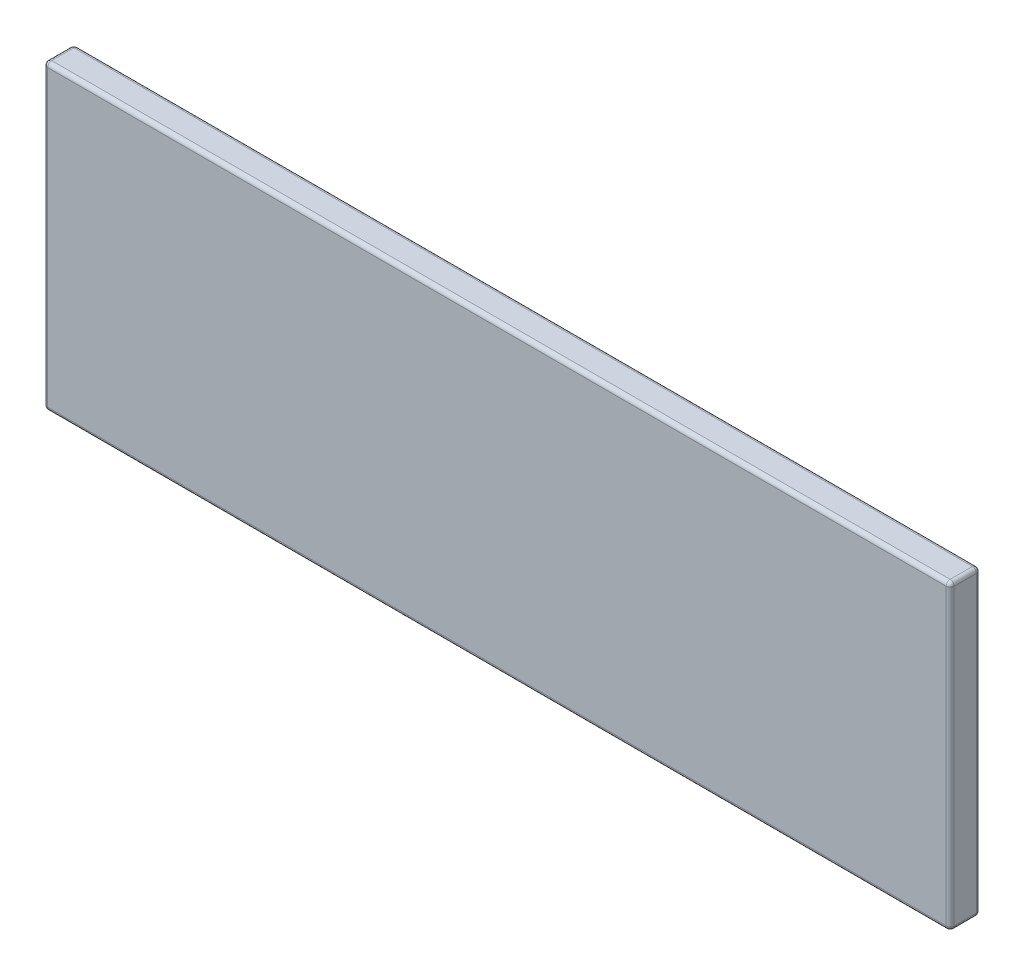
SolidWorks part; units mm, degrees
ref_plane "Front Plane" through (0, 0, 0) normal (0, 0, 1) x (1, 0, 0)
ref_plane "Top Plane" through (0, 0, 0) normal (0, 1, 0) x (1, 0, 0)
ref_plane "Right Plane" through (0, 0, 0) normal (1, 0, 0) x (0, 0, -1)
sketch "Sketch1" plane through (0, 0, 0) normal (0, 0, 1) x (1, 0, 0)
  line L1 (0, 0) -> (900, 0)
  line L2 (0, 0) -> (0, 300)
  line L3 (0, 300) -> (900, 300)
  line L4 (900, 0) -> (900, 300)
  dimension "D1" = 900
  dimension "D2" = 300
extrude "Boss-Extrude1" add sketch "Sketch1" along normal blind 30
fillet "Fillet1" radius 4 4 edges at (450, 300, 30) (900, 150, 30) (450, 0, 30) (0, 150, 30)
fillet "Fillet2" radius 4 4 edges at (450, 0, 0) (900, 150, 0) (450, 300, 0) (0, 150, 0)
fillet "Fillet3" radius 4 12 edges at (1.1716, 298.8284, 28.8284) (1.1716, 298.8284, 1.1716) (1.1716, 1.1716, 28.8284) (1.1716, 1.1716, 1.1716) (898.8284, 1.1716, 28.8284) (898.8284, 1.1716, 1.1716) (898.8284, 298.8284, 28.8284) (898.8284, 298.8284, 1.1716) (0, 300, 15) (0, 0, 15) (900, 0, 15) (900, 300, 15)
